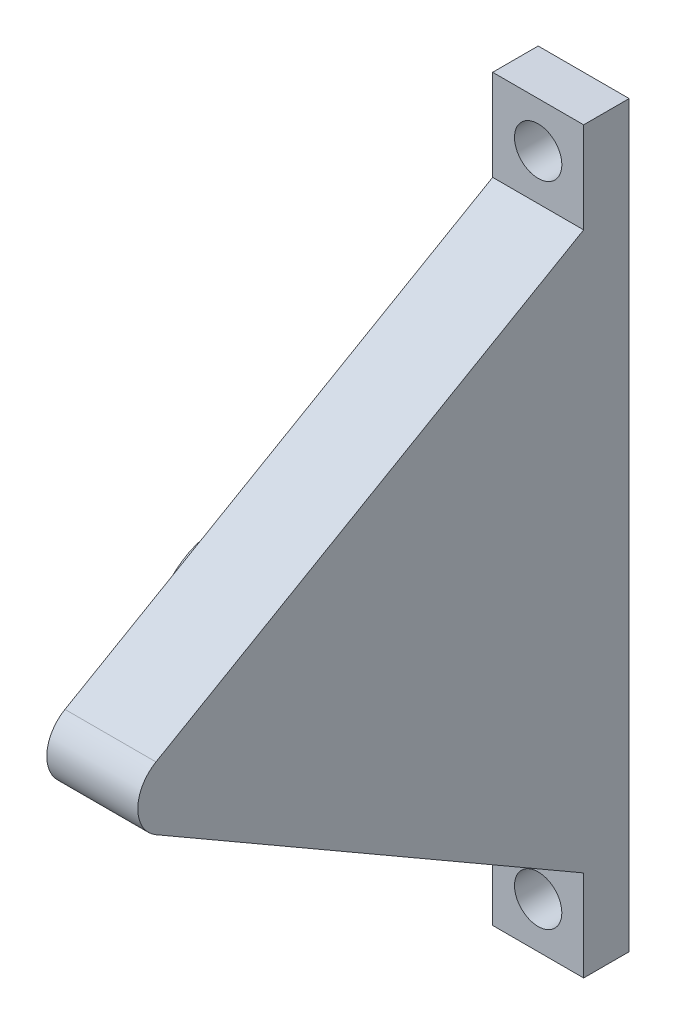
SolidWorks part; units mm, degrees
ref_plane "Front Plane" through (0, 0, 0) normal (0, 0, 1) x (1, 0, 0)
ref_plane "Top Plane" through (0, 0, 0) normal (0, 1, 0) x (1, 0, 0)
ref_plane "Right Plane" through (0, 0, 0) normal (1, 0, 0) x (0, 0, -1)
sketch "Sketch2" plane through (0, 0, 0) normal (1, 0, 0) x (0, 0, -1)
  line L0 (0, -103.1229) -> (0, 0)
  line L1 (0, 0) -> (-6.35, 0)
  line L2 (-6.35, 0) -> (-6.35, -12.7)
  line L3 (-6.35, -12.7) -> (-66.04, -47.162)
  line L4 (-66.04, -55.9609) -> (-6.35, -90.4229)
  line L5 (-6.35, -90.4229) -> (-6.35, -103.1229)
  line L6 (-6.35, -103.1229) -> (0, -103.1229)
  arc A0 (-66.04, -47.162) -> (-66.04, -55.9609) centre (-63.5, -51.5614) ccw
  point P7 (0, -51.5614)
  point P8 (-7.4155, -103.4444)
  point P9 (-8.1072, -107.6807)
  point P10 (-7.8027, -186.4327)
  point P13 (-73.66, -51.5614)
  point P14 (0, 0)
  point P17 (0, 0)
  dimension "D5" = 5.08
  dimension "D1" = 6.35
  dimension "D2" = 12.7
  dimension "D3" = 60
  dimension "D4" = 12.7
  dimension "D6" = 63.5
extrude "Boss-Extrude1" add sketch "Sketch2" along normal blind 12.7 contours L3 A0 L4 L5 L6 L0 L1 L2
sketch "Sketch3" plane through (0, 0, 0) normal (-1, 0, 0) x (0, 0, 1)
  line L0 (0, -103.1229) -> (0, 0) construction
  circle A0 centre (38.1, -51.5614) radius 9.398
  arc A1 (66.04, -55.9609) -> (66.04, -47.162) centre (63.5, -51.5614) ccw construction
  point P2 (0, 0)
  point P6 (68.58, -51.5614)
  dimension "D1" = 18.796
  dimension "D2" = 38.1
extrude "Boss-Extrude2" add sketch "Sketch3" along normal blind 6.35
sketch "Sketch4" plane through (0, 0, 6.35) normal (0, 0, 1) x (1, 0, 0)
  line L0 (12.7, -103.1229) -> (0, -103.1229) construction
  line L1 (12.7, -90.4229) -> (12.7, -103.1229) construction
  line L2 (12.7, -51.5614) -> (0, -51.5614) construction
  line L3 (12.7, -55.9609) -> (12.7, -47.162) construction
  line L4 (0, -47.162) -> (0, -55.9609) construction
  circle A0 centre (6.35, -96.7729) radius 3.302
  circle A1 centre (6.35, -6.35) radius 3.302
  point P4 (6.35, -103.1229)
  point P7 (12.7, -96.7729)
  dimension "D1" = 6.604
extrude "Cut-Extrude1" cut sketch "Sketch4" against normal through all
